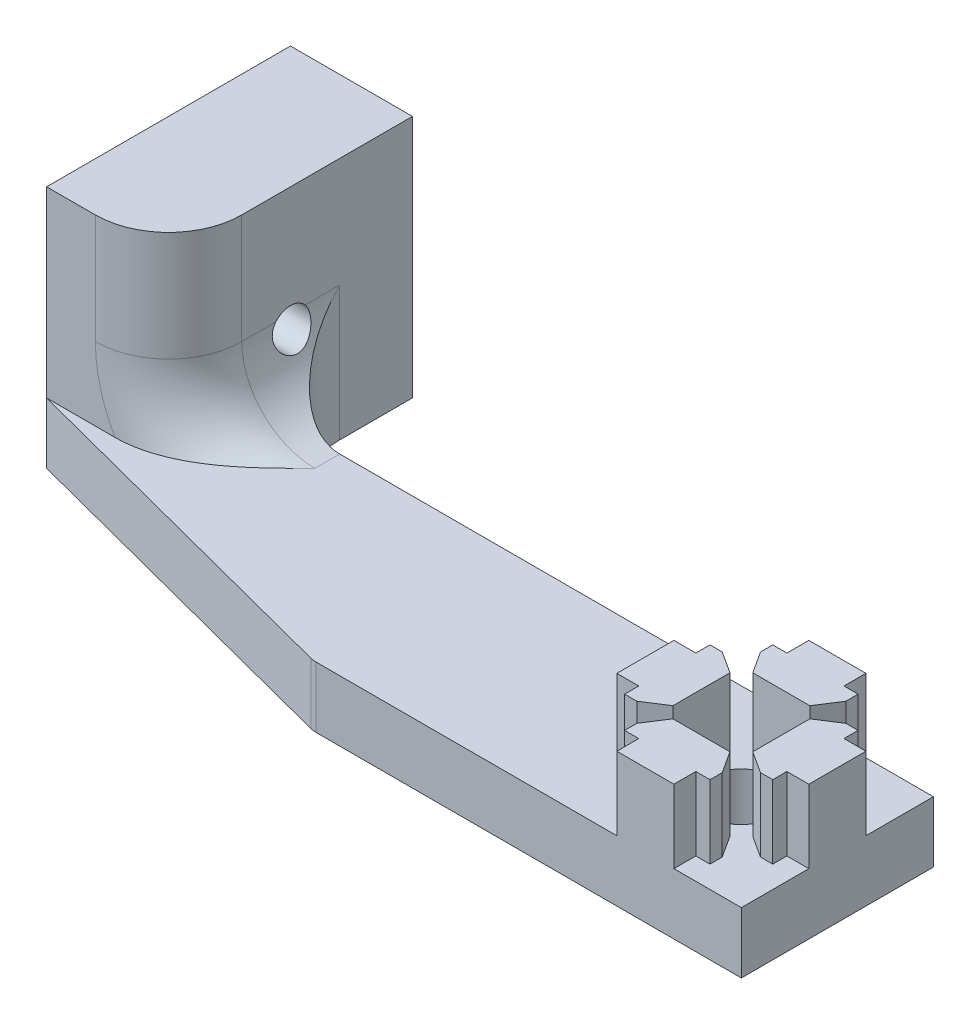
SolidWorks part; units mm, degrees
ref_plane "Front Plane" through (0, 0, 0) normal (0, 0, 1) x (1, 0, 0)
ref_plane "Top Plane" through (0, 0, 0) normal (0, 1, 0) x (1, 0, 0)
ref_plane "Right Plane" through (0, 0, 0) normal (1, 0, 0) x (0, 0, -1)
sketch "Sketch1" plane through (0, 0, 0) normal (0, 1, 0) x (1, 0, 0)
  line L0 (-2.9718, 10) -> (-2.9718, 7.714)
  line L1 (-10, 10) -> (10, 10)
  line L2 (-10, 10) -> (-10, -10)
  line L3 (-10, -10) -> (10, -10)
  line L4 (10, 10) -> (10, -10)
  line L5 (-10, 10) -> (10, -10) construction
  line L6 (-10, -10) -> (10, 10) construction
  line L7 (-2.9718, 10) -> (2.9718, 10) construction
  line L8 (-2.9718, 10) -> (-2.9718, 4.158) construction
  line L9 (-2.9718, 4.158) -> (2.9718, 4.158) construction
  line L10 (2.9718, 10) -> (2.9718, 4.158) construction
  line L11 (-4.445, 7.714) -> (4.445, 7.714) construction
  line L12 (-4.445, 7.714) -> (-4.445, 6.444) construction
  line L13 (-4.445, 6.444) -> (4.445, 6.444) construction
  line L14 (4.445, 7.714) -> (4.445, 6.444) construction
  line L15 (-4.445, 7.714) -> (4.445, 6.444) construction
  line L16 (-4.445, 6.444) -> (4.445, 7.714) construction
  line L17 (-2.9718, 7.714) -> (-4.445, 7.714)
  line L18 (-4.445, 7.714) -> (-4.445, 6.444)
  line L19 (-4.445, 6.444) -> (-2.9718, 4.158)
  line L20 (-2.9718, 4.158) -> (2.9718, 4.158)
  line L21 (2.9718, 4.158) -> (4.445, 6.444)
  line L22 (4.445, 6.444) -> (4.445, 7.714)
  line L23 (4.445, 7.714) -> (2.9718, 7.714)
  line L24 (2.9718, 7.714) -> (2.9718, 10)
  line L25 (2.9718, 10) -> (-2.9718, 10)
  line L26 (4.158, -2.9718) -> (4.158, 2.9718)
  line L27 (4.158, 2.9718) -> (6.444, 4.445)
  line L28 (6.444, 4.445) -> (7.714, 4.445)
  line L29 (7.714, 4.445) -> (7.714, 2.9718)
  line L30 (7.714, 2.9718) -> (10, 2.9718)
  line L31 (10, -2.9718) -> (10, 2.9718) construction
  line L32 (10, 2.9718) -> (10, -2.9718)
  line L33 (10, -2.9718) -> (7.714, -2.9718)
  line L34 (7.714, -2.9718) -> (7.714, -4.445)
  line L35 (7.714, -4.445) -> (6.444, -4.445)
  line L36 (6.444, -4.445) -> (4.158, -2.9718)
  line L37 (2.9718, -10) -> (-2.9718, -10) construction
  line L38 (4.445, -6.444) -> (2.9718, -4.158)
  line L39 (4.445, -7.714) -> (4.445, -6.444)
  line L40 (2.9718, -7.714) -> (4.445, -7.714)
  line L41 (2.9718, -10) -> (2.9718, -7.714)
  line L42 (-2.9718, -10) -> (2.9718, -10)
  line L43 (-2.9718, -7.714) -> (-2.9718, -10)
  line L44 (-4.445, -7.714) -> (-2.9718, -7.714)
  line L45 (-4.445, -6.444) -> (-4.445, -7.714)
  line L46 (-2.9718, -4.158) -> (-4.445, -6.444)
  line L47 (2.9718, -4.158) -> (-2.9718, -4.158)
  line L48 (-10, 2.9718) -> (-10, -2.9718) construction
  line L49 (-10, -2.9718) -> (-10, 2.9718)
  line L50 (-7.714, -2.9718) -> (-10, -2.9718)
  line L51 (-7.714, -4.445) -> (-7.714, -2.9718)
  line L52 (-6.444, -4.445) -> (-7.714, -4.445)
  line L53 (-4.158, -2.9718) -> (-6.444, -4.445)
  line L54 (-4.158, 2.9718) -> (-4.158, -2.9718)
  line L55 (-6.444, 4.445) -> (-4.158, 2.9718)
  line L56 (-7.714, 4.445) -> (-6.444, 4.445)
  line L57 (-7.714, 2.9718) -> (-7.714, 4.445)
  line L58 (-10, 2.9718) -> (-7.714, 2.9718)
  line L59 (0, 7.079) -> (0, 7.714) construction
  point P0 (0, 0)
  point P12 (0, 4.158)
  point P13 (0, 7.079)
  dimension "D3" = 10
  dimension "D1" = 20
  dimension "D2" = 20
  dimension "D4" = 5.9436
  dimension "D5" = 10
  dimension "D6" = 5.842
  dimension "D7" = 2.286
  dimension "D8" = 3.556
  dimension "D9" = 8.89
extrude "Boss-Extrude1" add sketch "Sketch1" along normal blind 7.62 contours L23 L24 L1 L0 L17 L18 L19 L20 L21 L22 | L26 L27 L28 L29 L30 L32 L33 L34 L35 L36 | L49 L58 L57 L56 L55 L54 L53 L52 L51 L50 | L38 L47 L46 L45 L44 L43 L42 L41 L40 L39 region at (0, 0, -6.9665)
sketch "Sketch2" plane through (0, 0, 0) normal (0, -1, 0) x (1, 0, 0)
  line L1 (10, -10) -> (-72.1538, -10)
  line L2 (10, -10) -> (10, 10)
  line L3 (10, 10) -> (-72.1538, 10)
  line L4 (-72.1538, -10) -> (-72.1538, 10)
  line L5 (10, -10) -> (-72.1538, 10) construction
  line L6 (10, 10) -> (-72.1538, -10) construction
  line L7 (-2.9718, -10) -> (2.9718, -10) construction
  line L8 (10, -2.9718) -> (10, 2.9718) construction
  dimension "D1" = 82.1538
  dimension "D2" = 20
  dimension "D3" = 0
  dimension "D4" = 0
extrude "Boss-Extrude2" add sketch "Sketch2" along normal blind 6.35
sketch "Sketch4" plane through (0, -6.35, 0) normal (0, -1, 0) x (-1, 0, 0)
  line L0 (72.1538, 10) -> (72.1538, -0.2108) construction
  line L1 (72.1538, -10) -> (72.1538, 10) construction
  line L2 (72.1538, -10) -> (34.6126, -10)
  line L3 (-10, -10) -> (72.1538, -10) construction
  line L4 (34.6126, -10) -> (72.1538, -0.2108)
  line L5 (72.1538, -0.2108) -> (72.1538, -10)
  dimension "D1" = 10.2108
  dimension "D2" = 37.5412
extrude "Cut-Extrude1" cut sketch "Sketch4" against normal through all
fillet "Fillet1" radius 2.54 1 edges at (-34.6126, -3.175, 10)
sketch "Sketch6" plane through (-72.1538, 0, 0) normal (-1, 0, 0) x (0, 0, 1)
  line L1 (0.2108, -6.35) -> (-25.1892, -6.35)
  line L2 (0.2108, -6.35) -> (0.2108, 19.05)
  line L3 (0.2108, 19.05) -> (-25.1892, 19.05)
  line L4 (-25.1892, -6.35) -> (-25.1892, 19.05)
  dimension "D1" = 25.4
  dimension "D2" = 25.4
extrude "Boss-Extrude7" add sketch "Sketch6" against normal blind 12.7
fillet "Fillet3" radius 7.62 2 edges at (-59.4538, 0, -4.8946) (-59.4538, -3.175, -10)
fillet "Fillet5" radius 7.62 2 edges at (-57.222, 2.2318, 0.2108) (-59.4538, 13.335, 0.2108)
sketch "Sketch11" plane through (-72.1538, 0, 0) normal (-1, 0, 0) x (0, 0, 1)
  line L0 (-25.1892, -6.35) -> (0.2108, 19.05) construction
  circle A0 centre (-12.4892, 6.35) radius 1.9844
  dimension "D1" = 3.9688
extrude "Cut-Extrude3" cut sketch "Sketch11" against normal through all
sketch "Sketch12" plane through (0, 0, 0) normal (0, 1, 0) x (1, 0, 0)
  circle A0 centre (0, 0) radius 3.556
  dimension "D1" = 7.112
extrude "Cut-Extrude4" cut sketch "Sketch12" against normal through all
